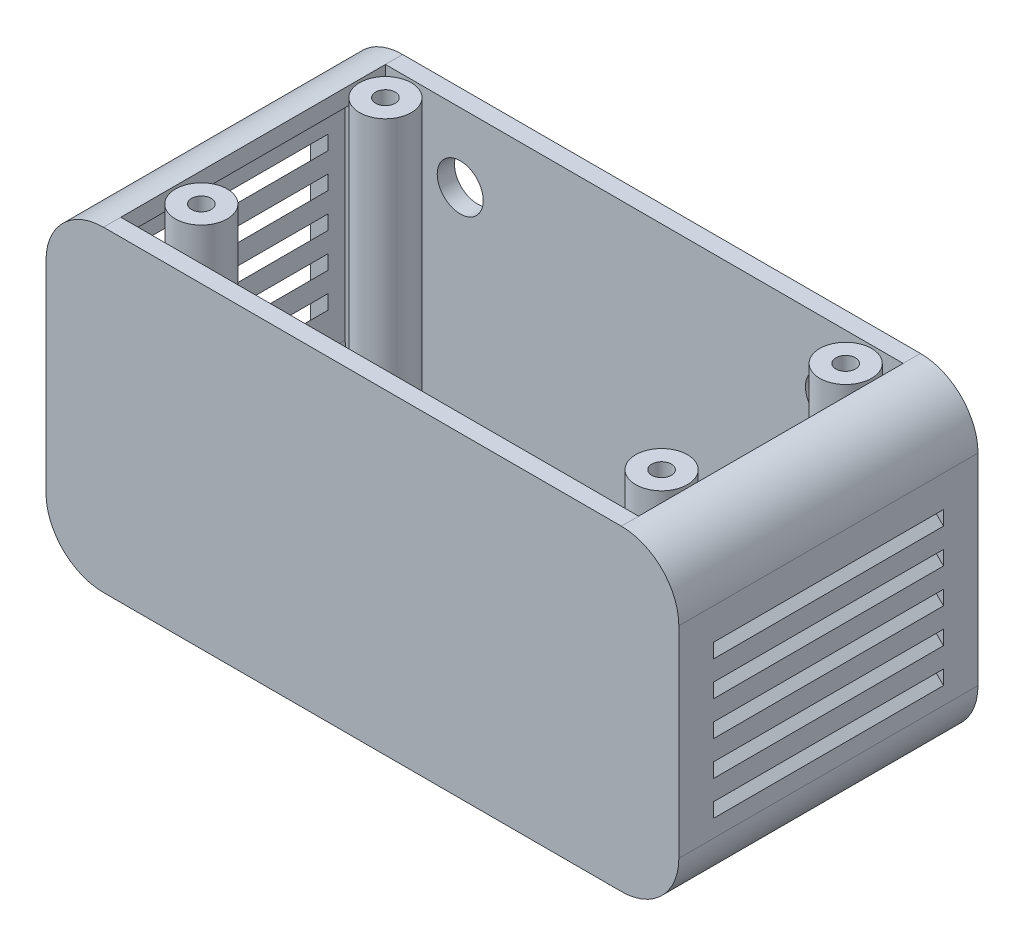
SolidWorks part; units mm, degrees
material "ABS"
ref_plane "Front Plane" through (0, 0, 0) normal (0, 0, 1) x (1, 0, 0)
ref_plane "Top Plane" through (0, 0, 0) normal (0, 1, 0) x (1, 0, 0)
ref_plane "Right Plane" through (0, 0, 0) normal (1, 0, 0) x (0, 0, -1)
sketch "Sketch1" plane through (0, 0, 0) normal (0, 0, 1) x (1, 0, 0)
  line L0 (-45, -55) -> (45, -55)
  line L1 (55, -45) -> (55, -10)
  line L2 (45, 0) -> (-45, 0)
  line L3 (-55, -10) -> (-55, -45)
  arc A0 (45, -55) -> (55, -45) centre (45, -45) ccw
  arc A1 (55, -10) -> (45, 0) centre (45, -10) ccw
  arc A2 (-45, 0) -> (-55, -10) centre (-45, -10) ccw
  arc A3 (-55, -45) -> (-45, -55) centre (-45, -45) ccw
extrude "Boss-Extrude1" add sketch "Sketch1" along normal blind 52
shell "Shell1" thickness 3 removed face at (0, 0, 26)
sketch "Sketch2" plane through (0, 0, 0) normal (0, 1, 0) x (1, 0, 0)
  circle A0 centre (-40, -8) radius 4.5
  circle A1 centre (40, -8) radius 4.5
  circle A2 centre (-40, -40) radius 4.5
  circle A3 centre (40, -40) radius 4.5
extrude "Boss-Extrude2" add sketch "Sketch2" against normal blind 52
sketch "Sketch3" plane through (0, -55, 0) normal (0, -1, 0) x (1, 0, 0)
  circle A0 centre (-40, 8) radius 3.25
  circle A1 centre (40, 8) radius 3.25
  circle A2 centre (-40, 40) radius 3.25
  circle A3 centre (40, 40) radius 3.25
extrude "Cut-Extrude1" cut sketch "Sketch3" against normal blind 49
sketch "Sketch4" plane through (0, -6, 0) normal (0, -1, 0) x (1, 0, 0)
  circle A0 centre (-40, 8) radius 1.7
  circle A1 centre (40, 8) radius 1.7
  circle A2 centre (-40, 40) radius 1.7
  circle A3 centre (40, 40) radius 1.7
extrude "Cut-Extrude2" cut sketch "Sketch4" against normal through all
ref_plane "Plane1" through (0, 0, 26) normal (0, 0, 1) x (1, 0, 0)
sketch "Sketch5" plane through (0, 0, 26) normal (0, 0, 1) x (1, 0, 0)
  line L0 (-51, -14) -> (-51, -11.5)
  line L1 (-51, -11.5) -> (-55.5, -16)
  line L2 (-55.5, -16) -> (-55.5, -18.5)
  line L3 (-55.5, -18.5) -> (-51, -14)
  line L4 (51, -14) -> (51, -11.5)
  line L5 (51, -11.5) -> (55.5, -16)
  line L6 (55.5, -16) -> (55.5, -18.5)
  line L7 (55.5, -18.5) -> (51, -14)
  line L8 (-51, -20) -> (-51, -17.5)
  line L9 (-51, -17.5) -> (-55.5, -22)
  line L10 (-55.5, -22) -> (-55.5, -24.5)
  line L11 (-55.5, -24.5) -> (-51, -20)
  line L12 (51, -20) -> (51, -17.5)
  line L13 (51, -17.5) -> (55.5, -22)
  line L14 (55.5, -22) -> (55.5, -24.5)
  line L15 (55.5, -24.5) -> (51, -20)
  line L16 (-51, -26) -> (-51, -23.5)
  line L17 (-51, -23.5) -> (-55.5, -28)
  line L18 (-55.5, -28) -> (-55.5, -30.5)
  line L19 (-55.5, -30.5) -> (-51, -26)
  line L20 (51, -26) -> (51, -23.5)
  line L21 (51, -23.5) -> (55.5, -28)
  line L22 (55.5, -28) -> (55.5, -30.5)
  line L23 (55.5, -30.5) -> (51, -26)
  line L24 (-51, -32) -> (-51, -29.5)
  line L25 (-51, -29.5) -> (-55.5, -34)
  line L26 (-55.5, -34) -> (-55.5, -36.5)
  line L27 (-55.5, -36.5) -> (-51, -32)
  line L28 (51, -32) -> (51, -29.5)
  line L29 (51, -29.5) -> (55.5, -34)
  line L30 (55.5, -34) -> (55.5, -36.5)
  line L31 (55.5, -36.5) -> (51, -32)
  line L32 (-51, -38) -> (-51, -35.5)
  line L33 (-51, -35.5) -> (-55.5, -40)
  line L34 (-55.5, -40) -> (-55.5, -42.5)
  line L35 (-55.5, -42.5) -> (-51, -38)
  line L36 (51, -38) -> (51, -35.5)
  line L37 (51, -35.5) -> (55.5, -40)
  line L38 (55.5, -40) -> (55.5, -42.5)
  line L39 (55.5, -42.5) -> (51, -38)
extrude "Cut-Extrude3" cut sketch "Sketch5" against normal blind 20 and the other way blind 20
sketch "Sketch6" plane through (0, -55, 0) normal (0, -1, 0) x (1, 0, 0)
  line L0 (-33, 12) -> (-33, 40) construction
  line L1 (-34.5, 12) -> (-34.5, 40)
  line L2 (-31.5, 12) -> (-31.5, 40)
  line L3 (-27, 12) -> (-27, 40) construction
  line L4 (-28.5, 12) -> (-28.5, 40)
  line L5 (-25.5, 12) -> (-25.5, 40)
  line L6 (-21, 12) -> (-21, 40) construction
  line L7 (-22.5, 12) -> (-22.5, 40)
  line L8 (-19.5, 12) -> (-19.5, 40)
  line L9 (-15, 12) -> (-15, 40) construction
  line L10 (-16.5, 12) -> (-16.5, 40)
  line L11 (-13.5, 12) -> (-13.5, 40)
  line L12 (-9, 12) -> (-9, 40) construction
  line L13 (-10.5, 12) -> (-10.5, 40)
  line L14 (-7.5, 12) -> (-7.5, 40)
  line L15 (-3, 12) -> (-3, 40) construction
  line L16 (-4.5, 12) -> (-4.5, 40)
  line L17 (-1.5, 12) -> (-1.5, 40)
  line L18 (33, 12) -> (33, 40) construction
  line L19 (31.5, 12) -> (31.5, 40)
  line L20 (34.5, 12) -> (34.5, 40)
  arc A0 (-34.5, 12) -> (-31.5, 12) centre (-33, 12) ccw
  arc A1 (-31.5, 40) -> (-34.5, 40) centre (-33, 40) ccw
  arc A2 (-28.5, 12) -> (-25.5, 12) centre (-27, 12) ccw
  arc A3 (-25.5, 40) -> (-28.5, 40) centre (-27, 40) ccw
  arc A4 (-22.5, 12) -> (-19.5, 12) centre (-21, 12) ccw
  arc A5 (-19.5, 40) -> (-22.5, 40) centre (-21, 40) ccw
  arc A6 (-16.5, 12) -> (-13.5, 12) centre (-15, 12) ccw
  arc A7 (-13.5, 40) -> (-16.5, 40) centre (-15, 40) ccw
  arc A8 (-10.5, 12) -> (-7.5, 12) centre (-9, 12) ccw
  arc A9 (-7.5, 40) -> (-10.5, 40) centre (-9, 40) ccw
  arc A10 (-4.5, 12) -> (-1.5, 12) centre (-3, 12) ccw
  arc A11 (-1.5, 40) -> (-4.5, 40) centre (-3, 40) ccw
  arc A12 (31.5, 12) -> (34.5, 12) centre (33, 12) ccw
  arc A13 (34.5, 40) -> (31.5, 40) centre (33, 40) ccw
  point P2 (-33, 26)
  point P7 (-27, 26)
  point P14 (-21, 26)
  point P21 (-15, 26)
  point P28 (-9, 26)
  point P35 (-3, 26)
  point P42 (33, 26)
extrude "Cut-Extrude4" cut sketch "Sketch6" against normal blind 3.5
sketch "Sketch7" plane through (0, 0, 0) normal (0, 0, -1) x (-1, 0, 0)
  circle A0 centre (32, -12) radius 4
  circle A1 centre (-32, -12) radius 4
extrude "Cut-Extrude5" cut sketch "Sketch7" against normal blind 3.5
sketch "Sketch8" plane through (0, -52, 0) normal (0, 1, 0) x (1, 0, 0)
  line L0 (-30.25, -26) -> (30.25, -26) construction
  line L1 (-47, -36) -> (-41, -36)
  line L2 (-47, -36) -> (-47, -16)
  line L3 (-47, -16) -> (-41, -16)
  line L4 (-41, -36) -> (-41, -16)
  line L5 (-47, -36) -> (-41, -16) construction
  line L6 (-47, -16) -> (-41, -36) construction
  point P0 (-44, -26)
extrude "Boss-Extrude3" add sketch "Sketch8" along normal blind 8
sketch "Sketch9" plane through (0, -44, 0) normal (0, 1, 0) x (1, 0, 0)
  line L0 (-30.25, -26) -> (30.25, -26) construction
  line L1 (-44.95, -34.3) -> (-43.05, -34.3)
  line L2 (-44.95, -34.3) -> (-44.95, -17.7)
  line L3 (-44.95, -17.7) -> (-43.05, -17.7)
  line L4 (-43.05, -34.3) -> (-43.05, -17.7)
  line L5 (-44.95, -34.3) -> (-43.05, -17.7) construction
  line L6 (-44.95, -17.7) -> (-43.05, -34.3) construction
  point P0 (-44, -26)
extrude "Cut-Extrude6" cut sketch "Sketch9" against normal blind 6
sketch "Sketch10" plane through (0, -52, 0) normal (0, 1, 0) x (1, 0, 0)
  circle A0 centre (15, -26) radius 15
  circle A1 centre (15, -26) radius 9.1
extrude "Boss-Extrude4" add sketch "Sketch10" along normal blind 8
sketch "Sketch11" plane through (0, -55, 0) normal (0, -1, 0) x (1, 0, 0)
  circle A0 centre (15, 26) radius 9.1
extrude "Cut-Extrude7" cut sketch "Sketch11" against normal blind 3.5
